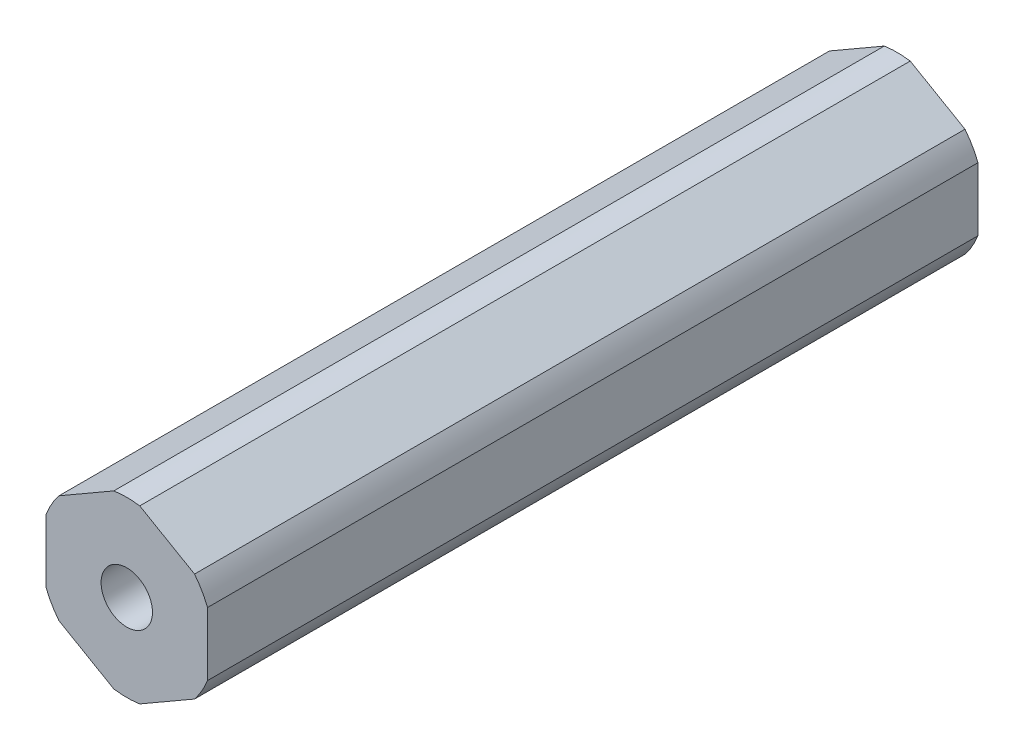
SolidWorks part; units mm, degrees
material "7075-T6 (SN)"
ref_plane "Front Plane" through (0, 0, 0) normal (0, 0, 1) x (1, 0, 0)
ref_plane "Top Plane" through (0, 0, 0) normal (0, 1, 0) x (1, 0, 0)
ref_plane "Right Plane" through (0, 0, 0) normal (1, 0, 0) x (0, 0, -1)
sketch "Sketch1" plane through (0, 0, 0) normal (0, 0, 1) x (1, 0, 0)
  line L1 (6.35, 3.6662) -> (0, 7.3323)
  line L2 (0, 7.3323) -> (-6.35, 3.6662)
  line L3 (-6.35, 3.6662) -> (-6.35, -3.6662)
  line L4 (-6.35, -3.6662) -> (0, -7.3323)
  line L5 (0, -7.3323) -> (6.35, -3.6662)
  line L6 (6.35, -3.6662) -> (6.35, 3.6662)
  circle A0 centre (0, 0) radius 6.35 construction
  circle A1 centre (0, 0) radius 6.8199
  dimension "D1" = 12.7
  dimension "D2" = 13.6398
extrude "Boss-Extrude1" add sketch "Sketch1" along normal mid plane 60.579 contours L6 A1 L1 L2 L3 L4 L5 region at (0, 0, 0)
hole_wizard "#10-32 Tapped Hole1" positions "Sketch2" profile "Sketch3" tap size "#10-32" standard "ANSI Inch"
sketch "Sketch2" plane through (0, 0, 30.2895) normal (0, 0, 1) x (1, 0, 0)
  point P0 (0, 0)
sketch "Sketch3" plane through (0, 0, 30.2895) normal (1, 0, 0) x (0, -1, 0)
  line L0 (0, 0) -> (0, 13.2428)
  line L1 (0, 13.2428) -> (2.0193, 12.0294)
  line L2 (2.0193, 12.0294) -> (2.0193, 0)
  line L5 (2.0193, 0) -> (0, 0)
  line L10 (0, 13.2428) -> (-2.0193, 12.0294) construction
  line L11 (0, -6.35) -> (0, 107.95) construction
  dimension "Tap Drill Dia." = 4.0386
  dimension "Tap Drill Depth" = 12.0294
  dimension "Drill Angle" = 118
cosmetic thread "Hole Thread1" parameters "D1"=9.652, "D2"=4.826
hole_wizard "#10-32 Tapped Hole2" positions "Sketch4" profile "Sketch5" tap size "#10-32" standard "ANSI Inch"
sketch "Sketch4" plane through (0, 0, -30.2895) normal (0, 0, -1) x (-1, 0, 0)
  point P0 (0, 0)
sketch "Sketch5" plane through (0, 0, -30.2895) normal (1, 0, 0) x (0, 1, 0)
  line L0 (0, 0) -> (0, 13.2428)
  line L1 (0, 13.2428) -> (2.0193, 12.0294)
  line L2 (2.0193, 12.0294) -> (2.0193, 0)
  line L5 (2.0193, 0) -> (0, 0)
  line L10 (0, 13.2428) -> (-2.0193, 12.0294) construction
  line L11 (0, -6.35) -> (0, 107.95) construction
  dimension "Tap Drill Dia." = 4.0386
  dimension "Tap Drill Depth" = 12.0294
  dimension "Drill Angle" = 118
cosmetic thread "Hole Thread2" parameters "D1"=9.652, "D2"=4.826
